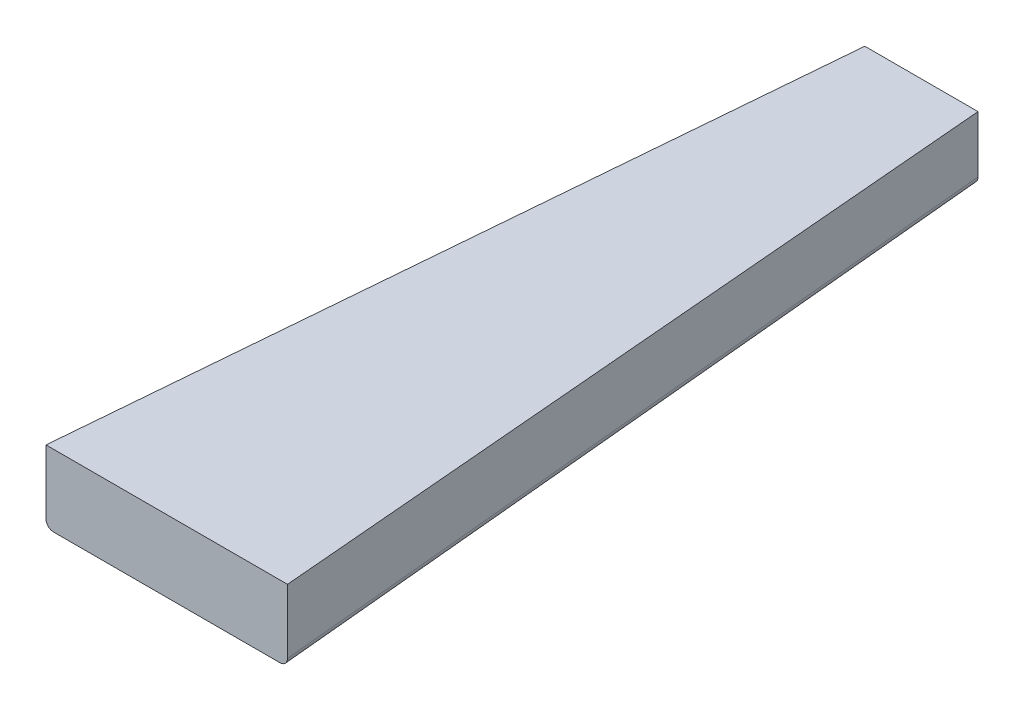
SolidWorks part; units mm, degrees
ref_plane "Front Plane" through (0, 0, 0) normal (0, 0, 1) x (1, 0, 0)
ref_plane "Top Plane" through (0, 0, 0) normal (0, 1, 0) x (1, 0, 0)
ref_plane "Right Plane" through (0, 0, 0) normal (1, 0, 0) x (0, 0, -1)
sketch "Sketch1" plane through (0, 0, 0) normal (0, 1, 0) x (1, 0, 0)
  line L0 (15, 0) -> (-15, 0)
  line L1 (0, 0) -> (0, -200) construction
  line L2 (32, -200) -> (-32, -200)
  line L3 (-32, -200) -> (-15, 0)
  line L4 (32, -200) -> (15, 0)
extrude "Boss-Extrude1" add sketch "Sketch1" along normal blind 19
sketch "Sketch4" plane through (0, 0, 0) normal (1, 0, 0) x (0, 0, -1)
  line L0 (-200, 0) -> (0, 0)
  line L1 (0, 0) -> (0, 2)
  line L2 (0, 19) -> (0, 0) construction
  line L4 (0, 2) -> (-200, 0)
extrude "Cut-Extrude1" cut sketch "Sketch4" against normal through all both and the other way through all
shell "Shell1" thickness 4 removed face at (0, 1, 100)
fillet "Fillet2" 2 edges at (23.5, 1, 100) (19.4856, 1, 100) type full round first side face at (23.5, 10, 100) second side face at (19.4856, 6, 100) middle face at (0, 1, 100)
fillet "Fillet3" 2 edges at (-23.5, 1, 100) (-19.4856, 1, 100) type full round first side face at (-23.5, 10, 100) second side face at (-19.4856, 6, 100) middle face at (0.0008, 1, 100)
